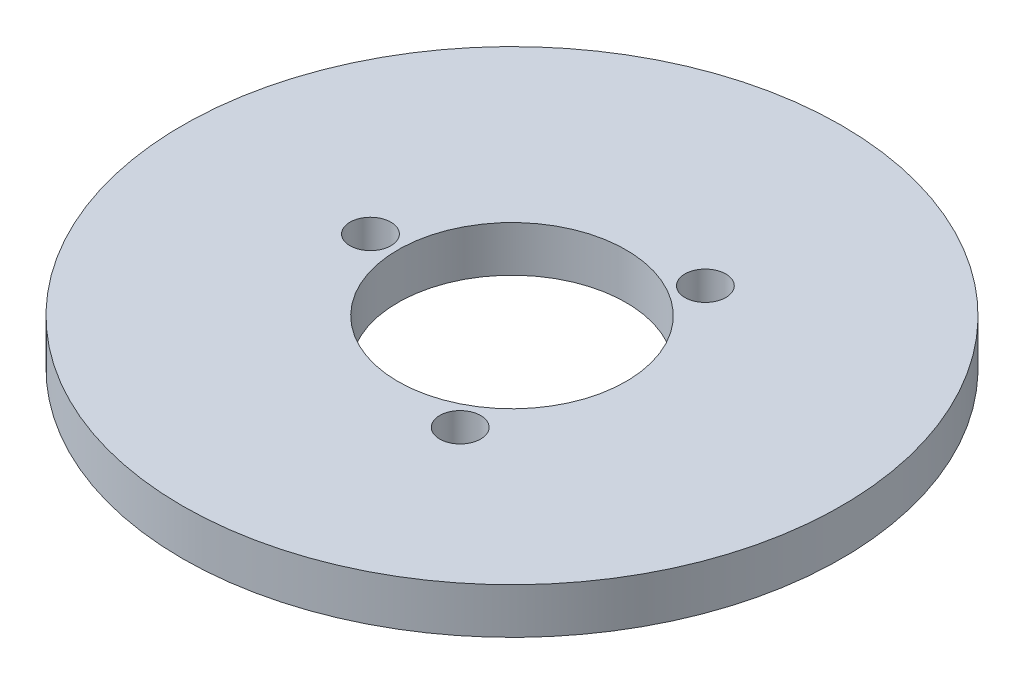
SolidWorks part; units mm, degrees
ref_plane "Front Plane" through (0, 0, 0) normal (0, 0, 1) x (1, 0, 0)
ref_plane "Top Plane" through (0, 0, 0) normal (0, 1, 0) x (1, 0, 0)
ref_plane "Right Plane" through (0, 0, 0) normal (1, 0, 0) x (0, 0, -1)
sketch "Sketch1" plane through (0, 0, 0) normal (0, 1, 0) x (1, 0, 0)
  circle A0 centre (0, 0) radius 65
  dimension "FLANGE_OD" = 130
extrude "Boss-Extrude1" add sketch "Sketch1" along normal blind 9
sketch "Sketch2" plane through (0, 0, 0) normal (0, 1, 0) x (1, 0, 0)
  circle A0 centre (0, 0) radius 22.5
  dimension "BORE_D" = 45
extrude "Cut-Extrude1" cut sketch "Sketch2" along normal through all
sketch "Sketch3" plane through (0, 9, 0) normal (0, 1, 0) x (1, 0, 0)
  circle A0 centre (0, 0) radius 27.917 construction
  circle A1 centre (-27.917, 0) radius 4.0366
  dimension "BOLT_D" = 8.0732
  dimension "BOLT_PCD" = 55.8341
extrude "Cut-Extrude2" cut sketch "Sketch3" against normal blind 8.8799
pattern_circular "CirPattern1" count 3 over 360 about axis through (0, 0, 0) along (0, 1, 0) of "Cut-Extrude2"
